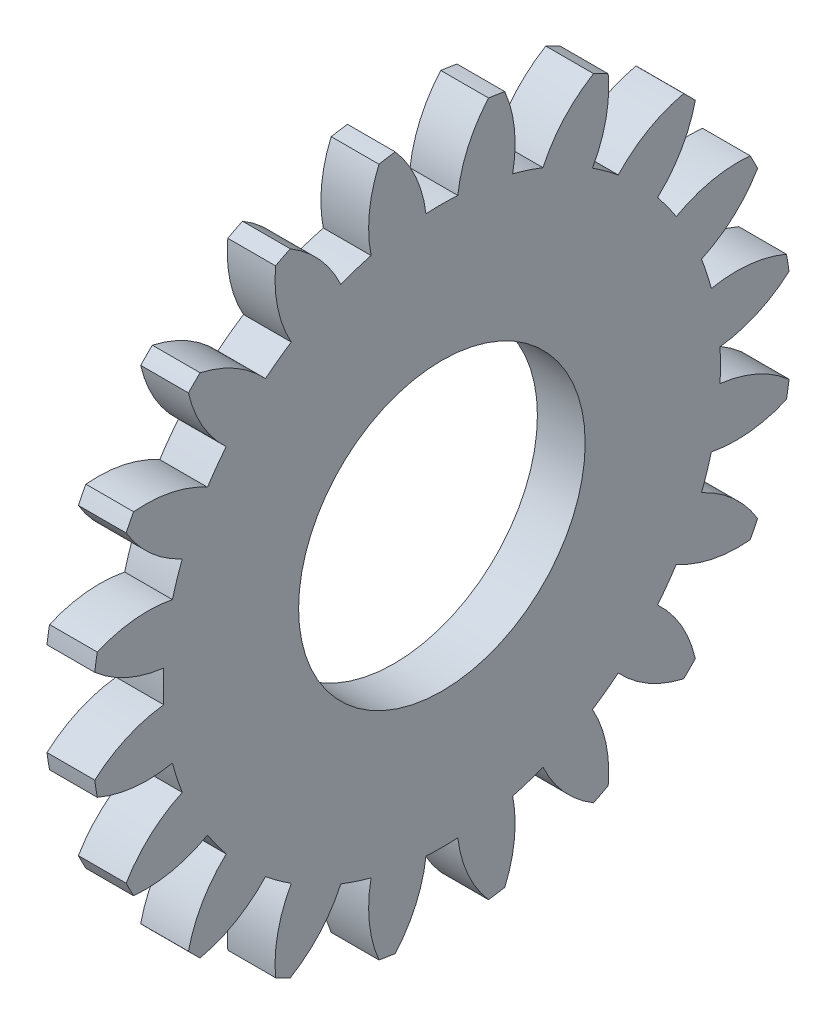
SolidWorks part; units mm, degrees
material "Zinc AC41A Alloy, As Cast"
ref_plane "Plane1" through (0, 0, 0) normal (0, 0, 1) x (1, 0, 0)
ref_plane "Plane2" through (0, 0, 0) normal (0, 1, 0) x (1, 0, 0)
ref_plane "Plane3" through (0, 0, 0) normal (1, 0, 0) x (0, 0, -1)
sketch "HoldingSke" plane through (0, 0, 0) normal (0, 1, 0) x (1, 0, 0)
  line L0 (0, 0) -> (0.9397, -0.342)
  line L1 (-15, 0) -> (100, 0) construction
  line L2 (0, 0) -> (-2.1039, 2.3779)
  line L3 (0, 0) -> (-11.863, 4.5341)
  line L4 (0, 0) -> (8.1152, 2.9537)
  line L5 (0, 0) -> (-46.8476, -17.4728)
  line L6 (0, 0) -> (-1.2434, -0.839)
  line L7 (-2.1039, 2.3779) -> (8.6586, 51.2059)
  line L8 (-76.2, 54.61) -> (-74.8, 54.61)
  line L9 (-71.009, 38.7566) -> (-53.1078, 45.2721)
  line L10 (-76.2, 71.12) -> (104.1128, 71.12)
  line L11 (0, 0) -> (-1.5, 0)
  line L12 (-76.2, 101.6) -> (-76.162, 101.6)
  line L13 (24.9733, 27.94) -> (52.9518, 28.4284)
  line L14 (24.9733, 27.94) -> (24.9743, 27.94)
  line L15 (24.9733, 27.94) -> (100.4006, 29.5858)
  line L16 (-63.627, -1) -> (-12.827, -1)
  circle A0 centre (0, 0) radius 4.5
  circle A1 centre (0, 0) radius 8.749
  circle A2 centre (0, 0) radius 37.5
  circle A3 centre (0, 0) radius 4.5
  dimension "Num_teeth" = 20
  dimension "Pitch_radius" = 180.3128
  dimension "Width" = 1.5
  dimension "Thickness" = 1.5
sketch "BasProSke" plane through (0, 0, 0) normal (0, 1, 0) x (1, 0, 0)
  line L0 (-10, 0) -> (60, 0) construction
  line L1 (0, 0) -> (0, 11)
  line L2 (0, 0) -> (1.5, 0)
  line L3 (1.5, 0) -> (1.5, 11)
  line L4 (1.5, 11) -> (0, 11)
  dimension "Thickness" = 1.5
  dimension "Diameter" = 22
revolve "Base-Revolve" add sketch "BasProSke" angle 360 about L0
sketch "TooCutSke" plane through (0, 0, 0) normal (1, 0, 0) x (0, 0, -1)
  line L1 (0, 0) -> (0, 107) construction
  line L2 (0, 0) -> (-0.8511, 9.9637) construction
  line L3 (0, 0) -> (-3.1206, 19.7028) construction
  line L4 (-0.8511, 9.9637) -> (-1.5603, 9.8514) construction
  arc A0 (0.4999, 8.7347) -> (-0.4999, 8.7347) centre (0, 0) ccw
  arc A1 (1.4852, 10.9249) -> (-1.4852, 10.9249) centre (0, 0) ccw
  circle A2 centre (0, 0) radius 10 construction
  circle A3 centre (0, 0) radius 9.3969 construction
  arc A4 (-0.4999, 8.7347) -> (-1.4852, 10.9249) centre (-4.4722, 8.2645) ccw
  arc A5 (1.4852, 10.9249) -> (0.4999, 8.7347) centre (4.4722, 8.2645) ccw
extrude "ToothCut" cut sketch "TooCutSke" along normal through all
fillet "Breaks" [suppressed] radius 0.02 tangent propagation no
fillet "RootFillets" [suppressed] radius 0.251
pattern_circular "TeethCuts" count 20 every 18 about axis through (-10, 0, 0) along (1, 0, 0) of "ToothCut", "RootFillets", "Breaks"
sketch "HubNeaOneSke" plane through (0, 0, 0) normal (-1, 0, 0) x (0, 0, 1)
  circle A0 centre (0, 0) radius 8.749
  dimension "Diameter" = 17.498
extrude "HubNearOne" [suppressed] add sketch "HubNeaOneSke" along normal blind 48.5001
sketch "HubNeaBotSke" plane through (0, 0, 0) normal (-1, 0, 0) x (0, 0, 1)
  circle A0 centre (0, 0) radius 8.749
  dimension "Diameter" = 17.498
extrude "HubNearBoth" [suppressed] add sketch "HubNeaBotSke" along normal blind 24.25
ref_plane "FarPln" through (1.5, 0, 0) normal (1, 0, 0) x (0, 0, -1)
sketch "HubFarSke" plane through (1.5, 0, 0) normal (1, 0, 0) x (0, 0, -1)
  circle A0 centre (0, 0) radius 8.749
  dimension "Diameter" = 17.498
extrude "HubFar" [suppressed] add sketch "HubFarSke" along normal blind 24.25
sketch "BorSke" plane through (0, 0, 0) normal (1, 0, 0) x (0, 0, -1)
  circle A0 centre (0, 0) radius 4.5
  dimension "Diameter" = 9
extrude "Bore" cut sketch "BorSke" along normal mid plane 100.0001
sketch "KeySke" plane through (0, 0, 0) normal (1, 0, 0) x (0, 0, -1)
  line L0 (-1.5, 0) -> (-1.5, 5.9)
  line L1 (-1.5, 5.9) -> (1.5, 5.9)
  line L2 (1.5, 5.9) -> (1.5, 0)
  line L3 (0, 0) -> (0, 34) construction
  line L4 (-1.5, 0) -> (1.5, 0)
  dimension "Width" = 3
extrude "Keyway" [suppressed] cut sketch "KeySke" along normal mid plane 100.0001
pattern_circular "Keyway2" [suppressed] count 2 every 90 about axis through (-10, 0, 0) along (1, 0, 0)
equation "' \"Module@HoldingSke\" = 6.35"
equation "' \"Num_teeth@HoldingSke\" = 12"
equation "' \"Ap@HoldingSke\" =  20"
equation "' \"Ap@HoldingSke\" = 20"
equation "' \"Width@HoldingSke\" = 0.5 * 25.4"
equation "' \"Hub_dia@HoldingSke\"= 1 * 25.4"
equation "' \"Hub_dia@HoldingSke\" = 1 * 25.4"
equation "' \"Overall_len@HoldingSke\" = 1.0 * 25.4"
equation "' \"Bore@HoldingSke\" = 0.75 * 25.4"
equation "' \"T_dim@HoldingSke\" = 0.1 * 25.4"
equation "' \"Width@KeySke\" = 0.25 * 25.4"
equation "' \"Show_teeth@HoldingSke\" = 13"
equation "' \"Backlash@HoldingSke\" = 0.009 * 25.4"
equation "' \"Addendum_fac@HoldingSke\" = 1.0"
equation "' \"Dedendum_fac@HoldingSke\" = 1.25"
equation "' \"Dedendum_add@HoldingSke\" = 0.00005 * 25.4"
equation "' \"Clearance_fac@HoldingSke\" = 0.25"
equation "\"Pitch@HoldingSke\" = 1 / \"Module@HoldingSke\""
equation "\"Overcut_dia@TooCutSke\" = (\"Num_teeth@HoldingSke\" + 2 * \"Addendum_fac@HoldingSke\") / \"Pitch@HoldingSke\" + 0.002 * 25.4"
equation "\"Pitch_dia@TooCutSke\" = \"Num_teeth@HoldingSke\" / \"Pitch@HoldingSke\""
equation "\"Base_dia@TooCutSke\" = \"Num_teeth@HoldingSke\" / \"Pitch@HoldingSke\" * cos((\"Ap@HoldingSke\"  * 3.14159265 / 180))"
equation "\"Root_dia@TooCutSke\" = (\"Num_teeth@HoldingSke\" + 2) / \"Pitch@HoldingSke\" - 2 * (\"Addendum_fac@HoldingSke\" + \"Dedendum_fac@HoldingSke\") / \"Pitch@HoldingSke\" - \"Dedendum_add@HoldingSke\" * 2"
equation "\"Half_ang@TooCutSke\" = 180 / \"Num_teeth@HoldingSke\""
equation "\"Half_CT@TooCutSke\" = \"Num_teeth@HoldingSke\" / \"Pitch@HoldingSke\" * sin((3.14159265 / 2 / \"Num_teeth@HoldingSke\")) / 2 - 7 * \"Backlash@HoldingSke\" / 4"
equation "\"Flank_rad@TooCutSke\" = \"Num_teeth@HoldingSke\" / \"Pitch@HoldingSke\" / 5"
equation "\"Radius@RootFillets\" = \"Clearance_fac@HoldingSke\" / \"Pitch@HoldingSke\" + \"Dedendum_add@HoldingSke\""
equation "\"Break_rad@Breaks\" = 0.02 / \"Pitch@HoldingSke\""
equation "\"Thickness@HoldingSke\" = \"Width@HoldingSke\""
equation "\"OAL@HoldingSke\" = \"Thickness@HoldingSke\""
equation "\"MHD@HoldingSke\" = (\"Num_teeth@HoldingSke\" + 2) / \"Pitch@HoldingSke\" - 2 * (\"Addendum_fac@HoldingSke\" + \"Dedendum_fac@HoldingSke\")  / \"Pitch@HoldingSke\" - \"Dedendum_add@HoldingSke\" * 2"
equation "\"MBD@HoldingSke\" = (\"Num_teeth@HoldingSke\" + 2) / \"Pitch@HoldingSke\" - 2 * (\"Addendum_fac@HoldingSke\" + \"Dedendum_fac@HoldingSke\")  / \"Pitch@HoldingSke\" - \"Dedendum_add@HoldingSke\" * 2 - 0.002 * 25.4"
equation "\"MHD@HoldingSke\" = ((sgn( \"MHD@HoldingSke\" - \"Hub_dia@HoldingSke\" )-1)*( \"MHD@HoldingSke\" - \"Hub_dia@HoldingSke\" ))/-2+ \"Hub_dia@HoldingSke\""
equation "\"MBD@HoldingSke\" = ((sgn( \"MBD@HoldingSke\" - \"Bore@HoldingSke\" )-1)*( \"MBD@HoldingSke\" - \"Bore@HoldingSke\" ))/-2+ \"Bore@HoldingSke\""
equation "\"OAL@HoldingSke\" = ((sgn( \"OAL@HoldingSke\" - \"Overall_len@HoldingSke\" )+1)*( \"OAL@HoldingSke\" - \"Overall_len@HoldingSke\" ))/2 + \"Overall_len@HoldingSke\" + 0.000002 * 25.4"
equation "\"Num_teeth@TeethCuts\" = int( \"Show_teeth@HoldingSke\" ) + 1"
equation "\"Num_teeth@TeethCuts\" = ((sgn( \"Num_teeth@TeethCuts\" - \"Num_teeth@HoldingSke\" )-1)*( \"Num_teeth@TeethCuts\" - \"Num_teeth@HoldingSke\" ))/-2+ \"Num_teeth@HoldingSke\""
equation "\"Num_teeth@TeethCuts\" = ((sgn( \"Num_teeth@TeethCuts\" - 2.0)+1)*( \"Num_teeth@TeethCuts\" - 2.0))/2 +2.0"
equation "\"Angle@TeethCuts\" = 360.0 / \"Num_teeth@HoldingSke\""
equation "\"Diameter@BasProSke\" = (\"Num_teeth@HoldingSke\" + 2 * \"Addendum_fac@HoldingSke\") / \"Pitch@HoldingSke\""
equation "\"Thickness@BasProSke\"  = \"Thickness@HoldingSke\""
equation "' \"Fillet_rad@BasProSke\" =  \"Thickness@HoldingSke\" * 0.05"
equation "' \"Fillet_rad@BasProSke\" = \"Thickness@HoldingSke\" * 0.05"
equation "\"MHD@HoldingSke\" = ((sgn( \"MHD@HoldingSke\" - \"Root_dia@TooCutSke\" )-1)*( \"MHD@HoldingSke\" - \"Root_dia@TooCutSke\" ))/-2+ \"Root_dia@TooCutSke\""
equation "\"Diameter@HubNeaOneSke\" = \"MHD@HoldingSke\""
equation "\"Length@HubNearOne\" = \"OAL@HoldingSke\" - \"Thickness@BasProSke\""
equation "\"Diameter@HubNeaBotSke\" = \"MHD@HoldingSke\""
equation "\"Length@HubNearBoth\" = ( \"OAL@HoldingSke\" - \"Thickness@BasProSke\" ) / 2.0"
equation "\"Thickness@FarPln\" = \"Thickness@BasProSke\""
equation "\"Diameter@HubFarSke\" = \"MHD@HoldingSke\""
equation "\"Length@HubFar\" = ( \"OAL@HoldingSke\" - \"Thickness@BasProSke\" ) / 2.0"
equation "\"Diameter@BorSke\" = \"MBD@HoldingSke\""
equation "\"D1@Bore\" = \"OAL@HoldingSke\" * 2.0"
equation "\"D1@Keyway\" = \"OAL@HoldingSke\" * 2.0"
equation "\"Offset@KeySke\" = \"T_dim@HoldingSke\" + \"MBD@HoldingSke\" / 2.0"
